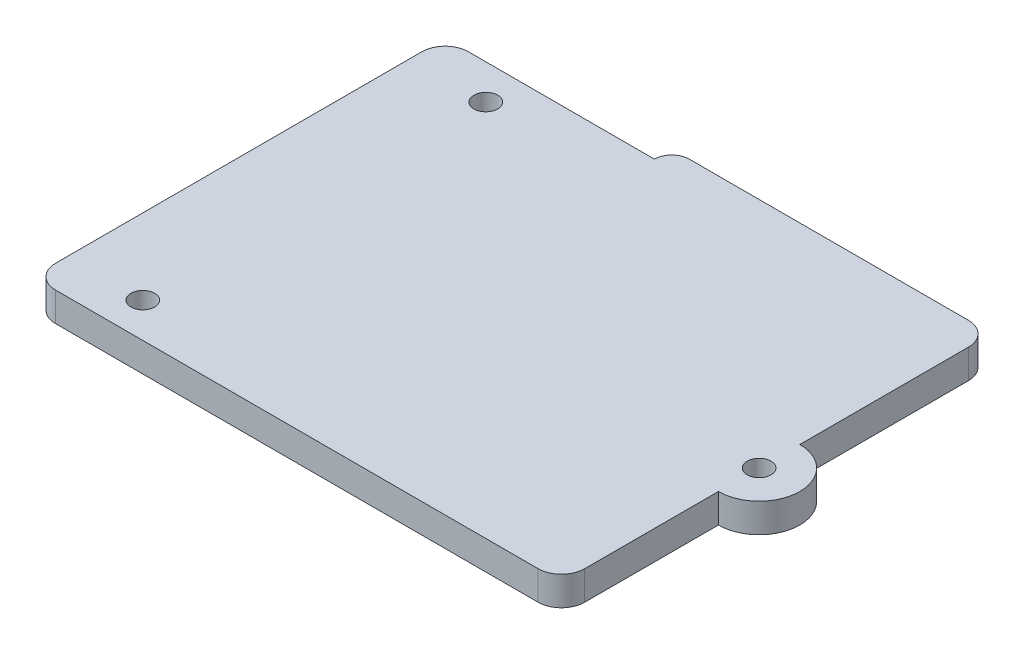
SolidWorks part; units mm, degrees
material "ABS"
ref_plane "Front Plane" through (0, 0, 0) normal (0, 0, 1) x (1, 0, 0)
ref_plane "Top Plane" through (0, 0, 0) normal (0, 1, 0) x (1, 0, 0)
ref_plane "Right Plane" through (0, 0, 0) normal (1, 0, 0) x (0, 0, -1)
sketch "Sketch1" plane through (0, 0, 0) normal (0, 1, 0) x (1, 0, 0)
  line L0 (0, 0) -> (45.5, 0)
  line L1 (45.5, 0) -> (45.5, 13.5)
  line L2 (45.5, 20.5) -> (45.5, 37)
  line L3 (45.5, 37) -> (18, 37)
  line L4 (18, 37) -> (18, 35.5)
  line L5 (18, 35.5) -> (0, 35.5)
  line L6 (0, 35.5) -> (0, 0)
  arc A0 (45.5, 13.5) -> (45.5, 20.5) centre (45.5, 17) ccw
  circle A1 centre (45.5, 17) radius 0.5
  circle A2 centre (6.5, 3) radius 0.5
  circle A3 centre (6.5, 32.5) radius 0.5
  dimension "D5" = 1
  dimension "D6" = 3.5
  dimension "D7" = 20
  dimension "D8" = 1
  dimension "D11" = 1
  dimension "D1" = 35.5
  dimension "D2" = 37
  dimension "D3" = 45.5
  dimension "D4" = 18
  dimension "D9" = 3
  dimension "D10" = 6.5
  dimension "D12" = 3
extrude "Boss-Extrude1" add sketch "Sketch1" along normal blind 2.5 contours A2 | A3 | A1 | L0 L1 A0 L2 L3 L4 L5 L6
fillet "Fillet1" radius 2 4 edges at (45.5, 1.25, -37) (45.5, 1.25, 0) (0, 1.25, 0) (0, 1.25, -35.5)
fillet "Fillet2" radius 1.5 1 edges at (18, 1.25, -37)
hole_wizard "M2.5x0.45 Tapped Hole1" positions "Sketch3" profile "Sketch2" tap size "M2.5x0.45" standard "ANSI Metric" end condition through all
sketch "Sketch3" plane through (0, 2.5, 0) normal (0, 1, 0) x (1, 0, 0)
  point P0 (6.5, 32.5)
  point P3 (6.5, 3)
  point P6 (45.5, 17)
sketch "Sketch2" plane through (6.5, 2.5, -32.5) normal (1, 0, 0) x (0, 0, 1)
  line L0 (0, 0) -> (0, 2.5)
  line L1 (0, 2.5) -> (1.025, 2.5)
  line L2 (1.025, 2.5) -> (1.025, 0)
  line L5 (1.025, 0) -> (0, 0)
  line L11 (0, -6.35) -> (0, 107.95) construction
  dimension "Thru Tap Drill Dia." = 2.05
  dimension "Thru Tap Drill Depth" = 2.5
cosmetic thread "Hole Thread1" parameters "D2"=2.5
cosmetic thread "Hole Thread2" parameters "D2"=2.5
cosmetic thread "Hole Thread3" parameters "D2"=2.5
